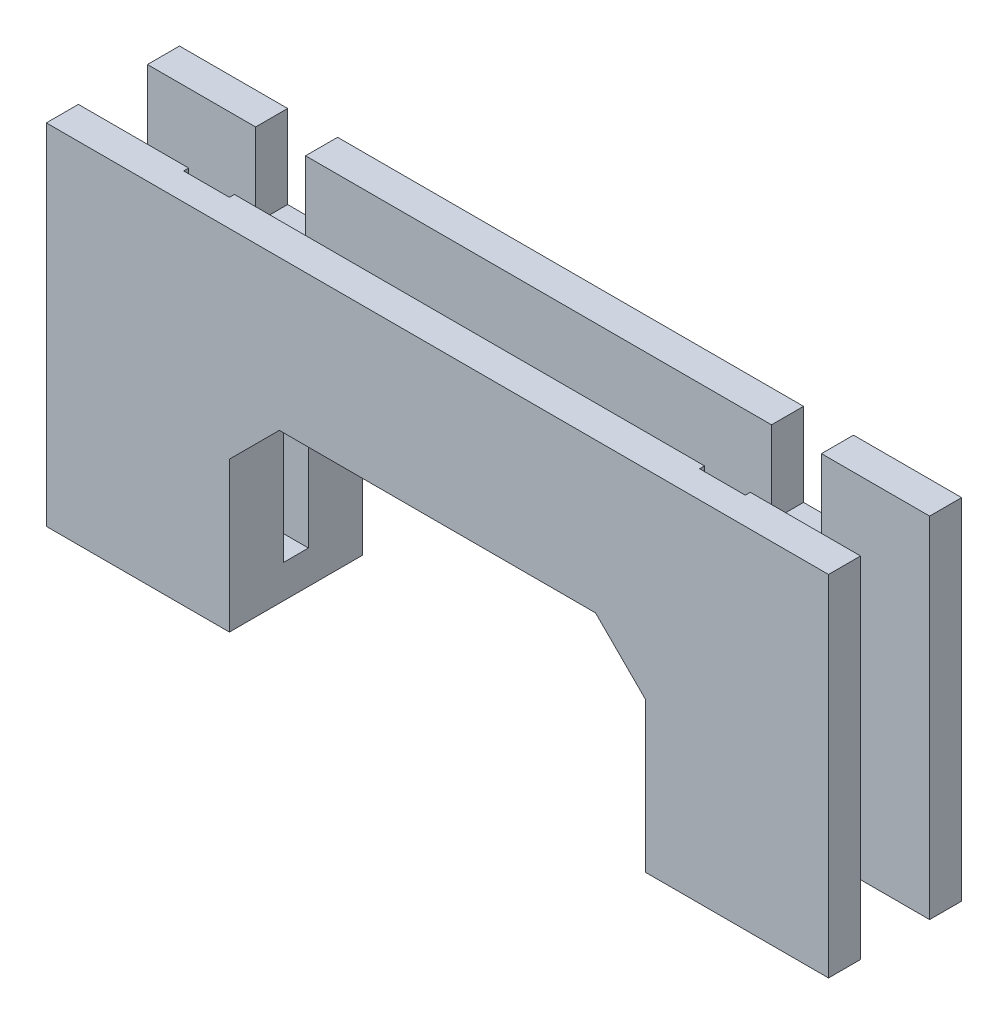
SolidWorks part; units mm, degrees
ref_plane "Спереди" through (0, 0, 0) normal (0, 0, 1) x (1, 0, 0)
ref_plane "Сверху" through (0, 0, 0) normal (0, 1, 0) x (1, 0, 0)
ref_plane "Справа" through (0, 0, 0) normal (1, 0, 0) x (0, 0, -1)
sketch "Эскиз1" plane through (0, 0, 0) normal (0, 0, 1) x (1, 0, 0)
  line L1 (-12.5, -6) -> (12.5, -6)
  line L2 (-12.5, -6) -> (-12.5, 6)
  line L3 (-12.5, 6) -> (12.5, 6)
  line L4 (12.5, -6) -> (12.5, 6)
  line L5 (-12.5, -6) -> (12.5, 6) construction
  line L6 (-12.5, 6) -> (12.5, -6) construction
  line L7 (-18.5, -6) -> (18.5, -6)
  line L8 (-18.5, -6) -> (-18.5, 10)
  line L9 (-18.5, 10) -> (18.5, 10)
  line L10 (18.5, -6) -> (18.5, 10)
  point P0 (0, 0)
  point P10 (0, 10)
  point P11 (0, 6)
  dimension "D1" = 25
  dimension "D2" = 12
  dimension "D3" = 6
  dimension "D4" = 16
extrude "Бобышка-Вытянуть1" add sketch "Эскиз1" along normal blind 8 contours L7 L10 L9 L8 L2 L3 L4
sketch "Эскиз2" plane through (0, -6, 0) normal (0, -1, 0) x (1, 0, 0)
  line L0 (-12.5, 8) -> (-12.5, 0) construction
  line L1 (-12.5, 3.25) -> (-14.125, 3.25)
  line L2 (-12.5, 3.25) -> (-12.5, 4.75)
  line L3 (-12.5, 4.75) -> (-14.125, 4.75)
  line L4 (-14.125, 3.25) -> (-14.125, 4.75)
  line L5 (-12.5, 8) -> (-12.5, 0) construction
  line L6 (-18.5, 8) -> (-18.5, 0) construction
  line L7 (-16.875, 1.625) -> (-14.125, 1.625)
  line L8 (-16.875, 1.625) -> (-16.875, 6.375)
  line L9 (-16.875, 6.375) -> (-14.125, 6.375)
  line L10 (-14.125, 1.625) -> (-14.125, 6.375)
  line L11 (-16.875, 1.625) -> (-14.125, 6.375) construction
  line L12 (-16.875, 6.375) -> (-14.125, 1.625) construction
  line L13 (-18.5, 8) -> (-12.5, 8) construction
  line L14 (0, -5.5) -> (0, 5.5) construction
  line L15 (16.875, 6.375) -> (14.125, 1.625) construction
  line L16 (16.875, 1.625) -> (14.125, 6.375) construction
  line L17 (14.125, 1.625) -> (14.125, 6.375)
  line L18 (16.875, 6.375) -> (14.125, 6.375)
  line L19 (16.875, 1.625) -> (16.875, 6.375)
  line L20 (16.875, 1.625) -> (14.125, 1.625)
  line L21 (14.125, 3.25) -> (14.125, 4.75)
  line L22 (12.5, 4.75) -> (14.125, 4.75)
  line L23 (12.5, 3.25) -> (12.5, 4.75)
  line L24 (12.5, 3.25) -> (14.125, 3.25)
  point P9 (-12.5, 4)
  point P10 (-15.5, 4)
  point P16 (-18.5, 4)
  point P19 (-15.5, 8)
  point P30 (15.5, 4)
  line M9 (12.5, 8) -> (12.5, 0)
  dimension "D1" = 1.5
  dimension "D2" = 4.75
  dimension "D3" = 2.75
extrude "Вырез-Вытянуть1" cut sketch "Эскиз2" against normal through all from offset 1 contours L20 L19 L18 L17 | L24 L17 L22 M9 | L4 L1 L2 L3 | L7 L10 L4 L9 L8 offset against normal yes
sketch "Эскиз3" plane through (0, -5, 0) normal (0, 1, 0) x (1, 0, 0)
  line L0 (-12.5, -3.25) -> (-14.125, -3.25) construction
  line L1 (-14.125, -1.625) -> (-14.625, -1.625)
  line L2 (-14.125, -1.625) -> (-14.125, -3.25)
  line L3 (-14.125, -3.25) -> (-14.625, -3.25)
  line L4 (-14.625, -1.625) -> (-14.625, -3.25)
  line L5 (-14.125, -6.375) -> (-14.625, -6.375)
  line L6 (-14.125, -6.375) -> (-14.125, -4.75)
  line L7 (-14.125, -4.75) -> (-14.625, -4.75)
  line L8 (-14.625, -6.375) -> (-14.625, -4.75)
  line L9 (0, -4.4) -> (0, 4.4) construction
  line L10 (14.625, -6.375) -> (14.625, -4.75)
  line L11 (14.125, -4.75) -> (14.625, -4.75)
  line L12 (14.125, -6.375) -> (14.125, -4.75)
  line L13 (14.125, -6.375) -> (14.625, -6.375)
  line L14 (14.625, -1.625) -> (14.625, -3.25)
  line L15 (14.125, -3.25) -> (14.625, -3.25)
  line L16 (14.125, -1.625) -> (14.125, -3.25)
  line L17 (14.125, -1.625) -> (14.625, -1.625)
  dimension "D1" = 0.5
extrude "Бобышка-Вытянуть2" add sketch "Эскиз3" along normal blind 2
chamfer "Фаска1" distance 1 angle 45 16 edges at (-14.125, -3, 5.5625) (-14.375, -3, 4.75) (-14.625, -3, 5.5625) (-14.375, -3, 6.375) (14.375, -3, 6.375) (14.625, -3, 5.5625) (14.375, -3, 4.75) (14.125, -3, 5.5625) (14.375, -3, 1.625) (14.125, -3, 2.4375) (14.375, -3, 3.25) (14.625, -3, 2.4375) (-14.125, -3, 2.4375) (-14.375, -3, 1.625) (-14.625, -3, 2.4375) (-14.375, -3, 3.25)
sketch "Эскиз4" plane through (0, -5, 0) normal (0, 1, 0) x (1, 0, 0)
  line L0 (-12.5, -4.75) -> (-14.625, -4.75) construction
  line L1 (-14.125, -4.75) -> (-12.5, -4.75)
  line L2 (-14.125, -4.75) -> (-14.125, -3.25)
  line L3 (-14.125, -3.25) -> (-12.5, -3.25)
  line L4 (-12.5, -4.75) -> (-12.5, -3.25)
  line L5 (0, -4.4) -> (0, 4.4) construction
  line L6 (12.5, -4.75) -> (12.5, -3.25)
  line L7 (14.125, -3.25) -> (12.5, -3.25)
  line L8 (14.125, -4.75) -> (14.125, -3.25)
  line L9 (14.125, -4.75) -> (12.5, -4.75)
extrude "Бобышка-Вытянуть3" add sketch "Эскиз4" along normal blind 1
chamfer "Фаска2" distance 3 angle 45 4 edges at (-12.5, 6, 1.625) (-12.5, 6, 6.375) (12.5, 6, 1.625) (12.5, 6, 6.375)
sketch "Эскиз5" plane through (0, -6, 0) normal (0, -1, 0) x (1, 0, 0)
  line L0 (-12.5, 8) -> (-12.5, 0) construction
  line L1 (-18.5, 8) -> (-23.5, 8)
  line L2 (-18.5, 8) -> (-18.5, 0)
  line L3 (-18.5, 0) -> (-23.5, 0)
  line L4 (-23.5, 8) -> (-23.5, 0)
  line L5 (-23.5, 1.925) -> (-18.5, 1.925)
  line L6 (-23.5, 1.925) -> (-23.5, 6.075)
  line L7 (-23.5, 6.075) -> (-18.5, 6.075)
  line L8 (-18.5, 1.925) -> (-18.5, 6.075)
  line L9 (0, -4.4) -> (0, 4.4) construction
  line L10 (18.5, 1.925) -> (18.5, 6.075)
  line L11 (23.5, 6.075) -> (18.5, 6.075)
  line L12 (23.5, 1.925) -> (23.5, 6.075)
  line L13 (23.5, 1.925) -> (18.5, 1.925)
  line L14 (23.5, 8) -> (23.5, 0)
  line L15 (18.5, 0) -> (23.5, 0)
  line L16 (18.5, 8) -> (18.5, 0)
  line L17 (18.5, 8) -> (23.5, 8)
  point P9 (-23.5, 4)
  point P13 (-12.5, 4)
  point P14 (-18.5, 4)
  line M8 (-18.5, 8) -> (-18.5, 0)
  dimension "D1" = 4.15
  dimension "D2" = 5
extrude "Бобышка-Вытянуть4" add sketch "Эскиз5" against normal through all contours L4 L7 L1 M8 | L5 L4 L3 L2 | L17 L16 L11 L14 | L13 L16 L15 L14
sketch "Эскиз6" plane through (0, 10, 0) normal (0, 1, 0) x (1, 0, 0)
  line L0 (-14.125, -4.75) -> (-14.125, -6.375) construction
  line L1 (-23.5, 0) -> (23.5, 0)
  line L2 (-23.5, 0) -> (-23.5, -1.925)
  line L3 (-23.5, -1.925) -> (23.5, -1.925)
  line L4 (23.5, 0) -> (23.5, -1.925)
  line L5 (-23.5, -6.075) -> (23.5, -6.075)
  line L6 (-23.5, -6.075) -> (-23.5, -8)
  line L7 (-23.5, -8) -> (23.5, -8)
  line L8 (23.5, -6.075) -> (23.5, -8)
  line L9 (-16.875, -6.375) -> (-14.125, -6.375) construction
  line L10 (-16.875, -6.375) -> (-14.625, -6.375) construction
  line L11 (-16.875, -1.625) -> (-16.875, -6.375) construction
  line L12 (-14.125, -1.625) -> (-14.125, -3.25) construction
  line L13 (-16.875, -1.625) -> (-14.125, -1.625) construction
  line L14 (14.125, -6.375) -> (14.125, -4.75) construction
  line L15 (16.875, -6.375) -> (14.125, -6.375) construction
  line L16 (16.875, -1.625) -> (16.875, -6.375) construction
  line L17 (16.875, -1.625) -> (14.125, -1.625) construction
  line L18 (14.125, -1.625) -> (14.125, -3.25) construction
  line L19 (-14.125, -4.75) -> (-14.125, -6.375)
  line L20 (-16.875, -6.375) -> (-14.125, -6.375)
  line L21 (-16.875, -6.375) -> (-14.625, -6.375)
  line L22 (-16.875, -1.625) -> (-16.875, -6.375)
  line L23 (-14.125, -1.625) -> (-14.125, -3.25)
  line L24 (-16.875, -1.625) -> (-14.125, -1.625)
  line L25 (14.125, -6.375) -> (14.125, -4.75)
  line L26 (16.875, -6.375) -> (14.125, -6.375)
  line L27 (16.875, -1.625) -> (16.875, -6.375)
  line L28 (16.875, -1.625) -> (14.125, -1.625)
  line L29 (14.125, -1.625) -> (14.125, -3.25)
  line L30 (0, -4.4) -> (0, 4.4) construction
  line L31 (-17, -1.925) -> (-14, -1.925)
  line L32 (-17, -1.925) -> (-17, 0)
  line L33 (-17, 0) -> (-14, 0)
  line L34 (-14, -1.925) -> (-14, 0)
  line L39 (14, -1.925) -> (14, 0)
  line L40 (17, 0) -> (14, 0)
  line L41 (17, -1.925) -> (17, 0)
  line L42 (17, -1.925) -> (14, -1.925)
  point P34 (-15.5, -1.925)
  point P35 (-15.5, -1.625)
  line M2 (-14.125, -4.75) -> (-14.125, -6.375)
  line M3 (-14.125, -6.375) -> (-16.875, -6.375)
  line M4 (-16.875, -6.375) -> (-16.875, -1.625)
  line M5 (-16.875, -1.625) -> (-14.125, -1.625)
  line M6 (-14.125, -1.625) -> (-14.125, -3.25)
  line M9 (23.5, 0) -> (-23.5, 0)
  line M10 (-23.5, 0) -> (-23.5, -1.925)
  line M11 (-23.5, -1.925) -> (-18.5, -1.925)
  line M13 (-18.5, -6.075) -> (-23.5, -6.075)
  line M14 (-23.5, -6.075) -> (-23.5, -8)
  line M15 (-23.5, -8) -> (23.5, -8)
  line M16 (23.5, -8) -> (23.5, -6.075)
  line M17 (23.5, -6.075) -> (18.5, -6.075)
  line M19 (18.5, -1.925) -> (23.5, -1.925)
  line M20 (23.5, -1.925) -> (23.5, 0)
  line M21 (14.125, -3.25) -> (14.125, -1.625)
  line M22 (14.125, -1.625) -> (16.875, -1.625)
  line M23 (16.875, -1.625) -> (16.875, -6.375)
  line M24 (16.875, -6.375) -> (14.125, -6.375)
  line M25 (14.125, -6.375) -> (14.125, -4.75)
  dimension "D2" = 3
extrude "Бобышка-Вытянуть5" add sketch "Эскиз6" along normal blind 5 contours L3 M11 M4 M5 M6 M21 M22 M23 M19 M20 M9 M10 | L5 L20 M13 M14 M15 M16 M17 M23 M24 M25 M2 M3 M4 | L3 L32 L1 M10 M11 | L41 L3 M19 M20 M9
sketch "Эскиз7" plane through (0, 6, 0) normal (0, -1, 0) x (1, 0, 0)
  line L0 (-6.25, 4) -> (6.25, 4) construction
  line L2 (0, 8) -> (0, 0) construction
  line L3 (-9.5, 8) -> (9.5, 8) construction
  circle A0 centre (-6.25, 4) radius 1.75
  circle A1 centre (6.25, 4) radius 1.75
  point P4 (0, 4)
  dimension "D2" = 3.5
  dimension "D1" = 12.5
extrude "Вырез-Вытянуть2" cut sketch "Эскиз7" against normal through all
